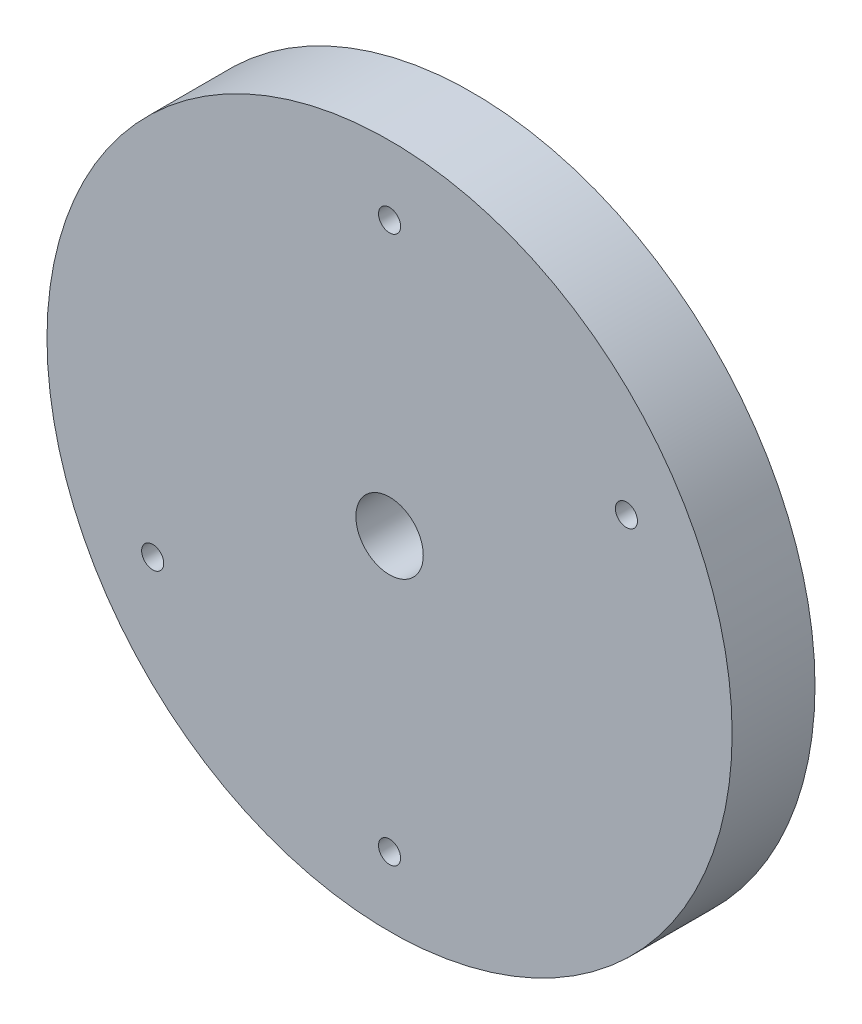
SolidWorks part; units mm, degrees
ref_plane "Front Plane" through (0, 0, 0) normal (0, 0, 1) x (1, 0, 0)
ref_plane "Top Plane" through (0, 0, 0) normal (0, 1, 0) x (1, 0, 0)
ref_plane "Right Plane" through (0, 0, 0) normal (1, 0, 0) x (0, 0, -1)
sketch "Sketch1" plane through (0, 0, 0) normal (0, 0, 1) x (1, 0, 0)
  circle A0 centre (0, 0) radius 62
  dimension "D1" = 124
extrude "Boss-Extrude1" add sketch "Sketch1" along normal blind 15 contours A0
sketch "Sketch2" plane through (0, 0, 15) normal (0, 0, 1) x (1, 0, 0)
  circle A0 centre (0, 49.5) radius 2
  dimension "D1" = 4
  dimension "D2" = 49.5
extrude "Cut-Extrude1" cut sketch "Sketch2" against normal blind 15
pattern_circular "CirPattern1" count 2 every 60 about axis through (0, 0, 15) along (0, 0, -1) of "Cut-Extrude1"
pattern_circular "CirPattern2" count 2 every 180 about axis through (0, 0, 15) along (0, 0, -1) of "CirPattern1", "Cut-Extrude1"
sketch "Sketch3" plane through (0, 0, 15) normal (0, 0, 1) x (1, 0, 0)
  circle A0 centre (0, 0) radius 6.1
  dimension "D1" = 12.2
extrude "Cut-Extrude2" cut sketch "Sketch3" against normal blind 15
